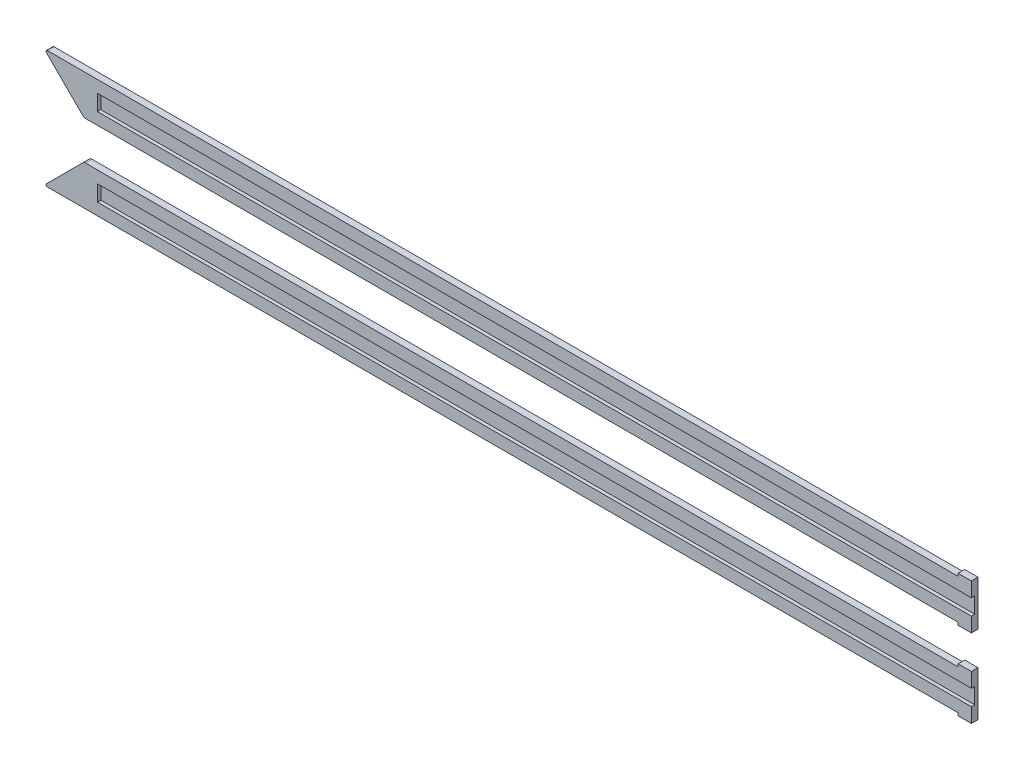
SolidWorks part; units mm, degrees
ref_plane "前视基准面" through (0, 0, 0) normal (0, 0, 1) x (1, 0, 0)
ref_plane "上视基准面" through (0, 0, 0) normal (0, 1, 0) x (1, 0, 0)
ref_plane "右视基准面" through (0, 0, 0) normal (1, 0, 0) x (0, 0, -1)
sketch "草图2" plane through (0, 0, 0) normal (0, 0, 1) x (1, 0, 0)
  line L0 (-81.1893, 42.8735) -> (-53.7751, 15.4593)
  line L1 (-80.4822, 44.5806) -> (616.8489, 44.5806)
  line L3 (-51.6538, 14.5806) -> (616.8489, 14.5806)
  line L4 (616.8489, 44.5806) -> (616.8489, 14.5806)
  line L5 (-40.6015, 347.7458) -> (356.0652, 347.7458) construction
  line L8 (606.8489, 44.5806) -> (616.8489, 44.5806)
  line L9 (606.8489, 44.5806) -> (606.8489, 46.5806)
  line L10 (606.8489, 46.5806) -> (616.8489, 46.5806)
  line L11 (616.8489, 44.5806) -> (616.8489, 46.5806)
  line L12 (616.8489, 14.5806) -> (606.8489, 14.5806)
  line L13 (616.8489, 14.5806) -> (616.8489, 12.5806)
  line L14 (616.8489, 12.5806) -> (606.8489, 12.5806)
  line L15 (606.8489, 14.5806) -> (606.8489, 12.5806)
  arc A0 (-80.4822, 44.5806) -> (-81.1893, 42.8735) centre (-80.4822, 43.5806) ccw
  arc A1 (-53.7751, 15.4593) -> (-51.6538, 14.5806) centre (-51.6538, 17.5806) ccw
  dimension "D2" = 1
  dimension "D3" = 3
  dimension "D1" = 45
extrude "凸台-拉伸1" add sketch "草图2" along normal blind 5 contours L3 L4 L1 A0 L0 A1 | L13 L12 L15 L14 | L9 L8 L11 L10
sketch "草图3" plane through (0, 0, 5) normal (0, 0, 1) x (1, 0, 0)
  line L1 (-42.6194, 35.5806) -> (617.3806, 35.5806)
  line L2 (-42.6194, 35.5806) -> (-42.6194, 23.5806)
  line L3 (-42.6194, 23.5806) -> (617.3806, 23.5806)
  line L4 (617.3806, 35.5806) -> (617.3806, 23.5806)
  line L6 (-80.4822, 44.5806) -> (606.8489, 44.5806) construction
  line L7 (-51.6538, 14.5806) -> (606.8489, 14.5806) construction
  dimension "D1" = 9
  dimension "D2" = 9
extrude "切除-拉伸1" cut sketch "草图3" against normal blind 2.5 contours L2 L1 L4 L3
mirror "镜向9" about plane through (0, 0, 0) normal (0, 1, 0) of bodies 102
